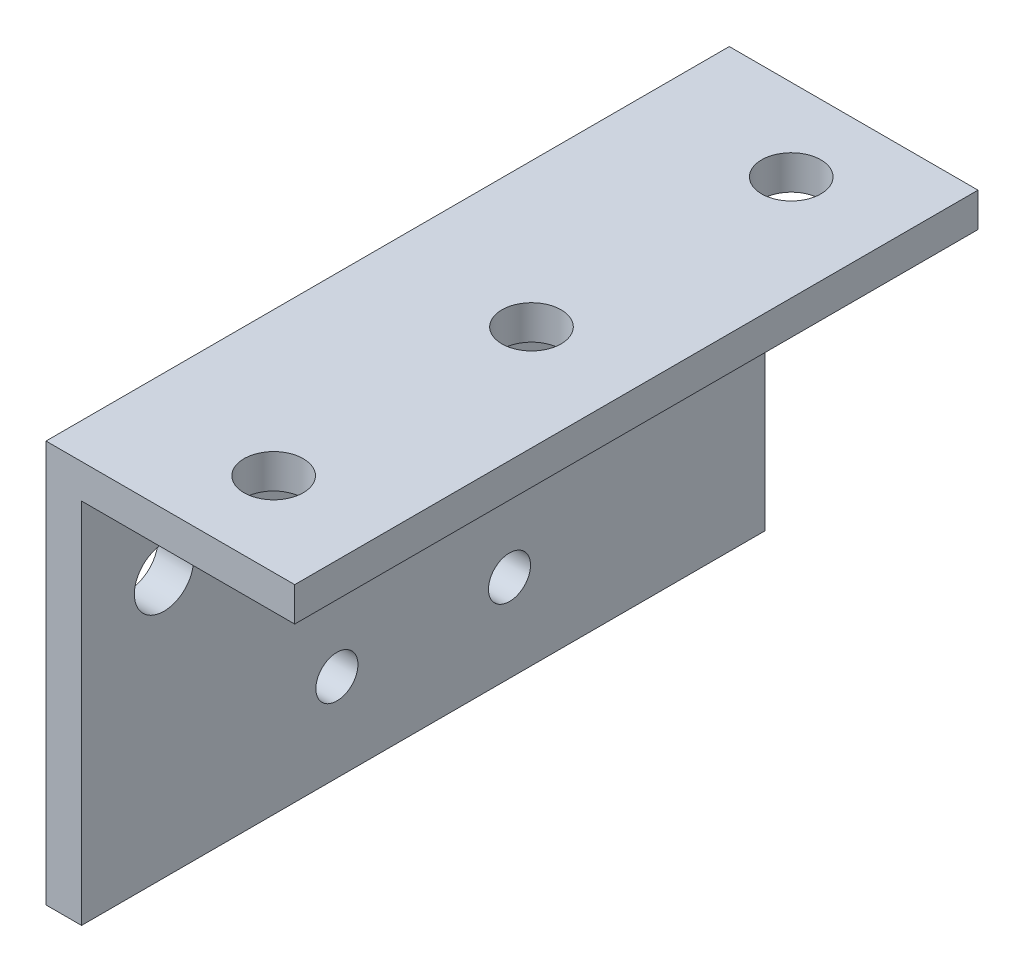
SolidWorks part; units mm, degrees
material "Alumina"
ref_plane "Front Plane" through (0, 0, 0) normal (0, 0, 1) x (1, 0, 0)
ref_plane "Top Plane" through (0, 0, 0) normal (0, 1, 0) x (1, 0, 0)
ref_plane "Right Plane" through (0, 0, 0) normal (1, 0, 0) x (0, 0, -1)
sketch "Sketch1" plane through (0, 0, 0) normal (0, 0, 1) x (1, 0, 0)
  line L0 (0, 0) -> (0, 37.338)
  line L1 (0, 37.338) -> (23.114, 37.338)
  line L2 (23.114, 37.338) -> (23.114, 34.163)
  line L3 (0, 0) -> (3.302, 0)
  line L4 (3.302, 0) -> (3.302, 34.163)
  line L5 (3.302, 34.163) -> (23.114, 34.163)
  dimension "D1" = 37.338
  dimension "D2" = 23.114
  dimension "D3" = 3.175
extrude "Boss-Extrude1" add sketch "Sketch1" along normal blind 63.5
sketch "Sketch21" plane through (0, 0, 0) normal (-1, 0, 0) x (0, 0, 1)
  line L0 (31.75, 0) -> (31.75, 37.338) construction
  line L1 (63.5, 0) -> (0, 0) construction
  line L2 (63.5, 37.338) -> (0, 37.338) construction
  point P3 (31.75, 18.669)
sketch "Sketch28" plane through (0, 37.338, 0) normal (0, 1, 0) x (1, 0, 0)
  line L0 (23.114, -31.75) -> (0, -31.75) construction
  line L2 (23.114, -63.5) -> (23.114, 0) construction
  point P3 (11.557, -31.75)
sketch "Sketch29" plane through (0, 0, 0) normal (-1, 0, 0) x (0, 0, 1)
  line L0 (0, 24.2082) -> (63.5, 24.2082) construction
  line L1 (0, 37.338) -> (0, 0) construction
  line L2 (63.5, 37.338) -> (63.5, 0) construction
sketch "Sketch30" plane through (0, 37.338, 0) normal (0, 1, 0) x (1, 0, 0)
  line L0 (13.3686, 0) -> (13.3686, -63.5) construction
  line L1 (23.114, 0) -> (0, 0) construction
  line L2 (23.114, -63.5) -> (0, -63.5) construction
sketch "Sketch31" plane through (0, 0, 0) normal (-1, 0, 0) x (0, 0, 1)
  line L0 (31.75, 24.2082) -> (10.16, 24.2082) construction
  line L1 (0, 24.2082) -> (63.5, 24.2082) construction
  line L2 (31.75, 24.2082) -> (53.34, 24.2082) construction
sketch "Sketch32" plane through (0, 37.338, 0) normal (0, 1, 0) x (1, 0, 0)
  line L0 (13.3686, -31.75) -> (13.3686, -53.34) construction
  line L1 (13.3686, 0) -> (13.3686, -63.5) construction
  line L2 (13.3686, -31.75) -> (13.3686, -10.16) construction
hole_wizard "M5 Clearance Hole1" positions "Sketch35" profile "Sketch36" hole size "M5" standard "ANSI Metric" end condition through all
sketch "Sketch35" plane through (0, 0, 0) normal (-1, 0, 0) x (0, 0, 1)
  line L0 (0, 24.2082) -> (63.5, 24.2082) construction
  point P0 (55.8413, 24.2082)
sketch "Sketch36" plane through (0, 24.2082, 55.8413) normal (0, 1, 0) x (0, 0, 1)
  line L0 (0, 0) -> (0, 23.114)
  line L1 (0, 23.114) -> (2.75, 23.114)
  line L2 (2.75, 23.114) -> (2.75, 0)
  line L5 (2.75, 0) -> (0, 0)
  line L11 (0, -6.35) -> (0, 107.95) construction
  dimension "Thru Hole Dia." = 5.5
  dimension "Thru Hole Depth" = 23.114
hole_wizard "M5 Clearance Hole2" positions "Sketch37" profile "Sketch38" hole size "M5" standard "ANSI Metric" end condition through all
sketch "Sketch37" plane through (0, 0, 0) normal (-1, 0, 0) x (0, 0, 1)
  line L0 (0, 24.2082) -> (63.5, 24.2082) construction
  point P0 (7.6776, 24.2082)
sketch "Sketch38" plane through (0, 24.2082, 7.6776) normal (0, 1, 0) x (0, 0, 1)
  line L0 (0, 0) -> (0, 23.114)
  line L1 (0, 23.114) -> (2.75, 23.114)
  line L2 (2.75, 23.114) -> (2.75, 0)
  line L5 (2.75, 0) -> (0, 0)
  line L11 (0, -6.35) -> (0, 107.95) construction
  dimension "Thru Hole Dia." = 5.5
  dimension "Thru Hole Depth" = 23.114
hole_wizard "M5 Clearance Hole3" positions "Sketch39" profile "Sketch40" hole size "M5" standard "ANSI Metric" end condition through all
sketch "Sketch39" plane through (0, 37.338, 0) normal (0, 1, 0) x (1, 0, 0)
  point P0 (13.3686, -31.75)
sketch "Sketch40" plane through (13.3686, 37.338, 31.75) normal (1, 0, 0) x (0, 0, 1)
  line L0 (0, 0) -> (0, 37.338)
  line L1 (0, 37.338) -> (2.75, 37.338)
  line L2 (2.75, 37.338) -> (2.75, 0)
  line L5 (2.75, 0) -> (0, 0)
  line L11 (0, -6.35) -> (0, 107.95) construction
  dimension "Thru Hole Dia." = 5.5
  dimension "Thru Hole Depth" = 37.338
hole_wizard "M5 Clearance Hole4" positions "Sketch43" profile "Sketch44" hole size "M5" standard "ANSI Metric" end condition through all
sketch "Sketch43" plane through (0, 37.338, 0) normal (0, 1, 0) x (1, 0, 0)
  line L0 (13.3686, 0) -> (13.3686, -63.5) construction
  point P0 (13.3686, -55.7137)
sketch "Sketch44" plane through (13.3686, 37.338, 55.7137) normal (1, 0, 0) x (0, 0, 1)
  line L0 (0, 0) -> (0, 37.338)
  line L1 (0, 37.338) -> (2.75, 37.338)
  line L2 (2.75, 37.338) -> (2.75, 0)
  line L5 (2.75, 0) -> (0, 0)
  line L11 (0, -6.35) -> (0, 107.95) construction
  dimension "Thru Hole Dia." = 5.5
  dimension "Thru Hole Depth" = 37.338
hole_wizard "#23 (0.154) Diameter Hole1" positions "Sketch45" profile "Sketch46" hole size "#23" standard "ANSI Inch" end condition through all
sketch "Sketch45" plane through (0, 0, 0) normal (-1, 0, 0) x (0, 0, 1)
  point P0 (39.768, 8.1615)
  point P3 (23.7266, 8.1424)
  point P5 (23.7266, 24.1476)
  point P7 (39.7208, 24.1476)
sketch "Sketch46" plane through (0, 8.1615, 39.768) normal (0, 1, 0) x (0, 0, 1)
  line L0 (0, 0) -> (0, 23.114)
  line L1 (0, 23.114) -> (1.9558, 23.114)
  line L2 (1.9558, 23.114) -> (1.9558, 0)
  line L5 (1.9558, 0) -> (0, 0)
  line L11 (0, -6.35) -> (0, 107.95) construction
  dimension "Thru Hole Dia." = 3.9116
  dimension "Thru Hole Depth" = 23.114
hole_wizard "M5 Clearance Hole5" positions "Sketch49" profile "Sketch50" hole size "M5" standard "ANSI Metric" end condition through all
sketch "Sketch49" plane through (0, 37.338, 0) normal (0, 1, 0) x (1, 0, 0)
  line L0 (13.3686, 0) -> (13.3686, -63.5) construction
  point P0 (13.3686, -7.6106)
sketch "Sketch50" plane through (13.3686, 37.338, 7.6106) normal (1, 0, 0) x (0, 0, 1)
  line L0 (0, 0) -> (0, 37.338)
  line L1 (0, 37.338) -> (2.75, 37.338)
  line L2 (2.75, 37.338) -> (2.75, 0)
  line L5 (2.75, 0) -> (0, 0)
  line L11 (0, -6.35) -> (0, 107.95) construction
  dimension "Thru Hole Dia." = 5.5
  dimension "Thru Hole Depth" = 37.338
